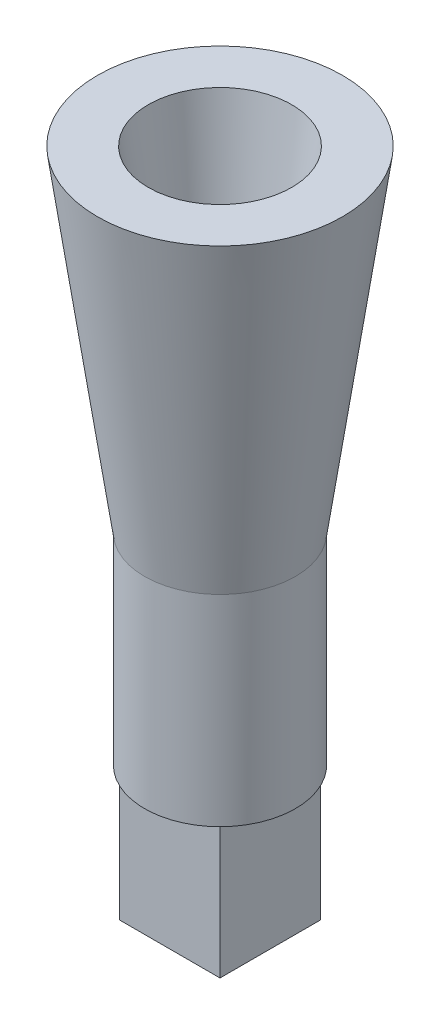
SolidWorks part; units mm, degrees
ref_plane "Front Plane" through (0, 0, 0) normal (0, 0, 1) x (1, 0, 0)
ref_plane "Top Plane" through (0, 0, 0) normal (0, 1, 0) x (1, 0, 0)
ref_plane "Right Plane" through (0, 0, 0) normal (1, 0, 0) x (0, 0, -1)
sketch "Sketch1" plane through (0, 0, 0) normal (0, 1, 0) x (1, 0, 0)
  line L1 (-38.1, 38.1) -> (38.1, 38.1)
  line L2 (-38.1, 38.1) -> (-38.1, -38.1)
  line L3 (-38.1, -38.1) -> (38.1, -38.1)
  line L4 (38.1, 38.1) -> (38.1, -38.1)
  line L5 (-38.1, 38.1) -> (38.1, -38.1) construction
  line L6 (-38.1, -38.1) -> (38.1, 38.1) construction
  point P0 (0, 0)
  dimension "D1" = 76.2
  dimension "D2" = 76.2
extrude "Boss-Extrude1" add sketch "Sketch1" along normal blind 101.6
sketch "Sketch2" plane through (0, 101.6, 0) normal (0, 1, 0) x (1, 0, 0)
  circle A0 centre (0, 0) radius 57.15
  dimension "D1" = 114.3
extrude "Boss-Extrude2" add sketch "Sketch2" along normal blind 152.4
sketch "Sketch4" plane through (0, 254, 0) normal (0, 1, 0) x (1, 0, 0)
  circle A0 centre (0, 0) radius 57.15
  dimension "D1" = 114.3
extrude "Boss-Extrude3" add sketch "Sketch4" along normal blind 254 draft 8 draft outward yes
shell "Shell1" thickness 38.1 removed face at (0, 508, 92.8474)
